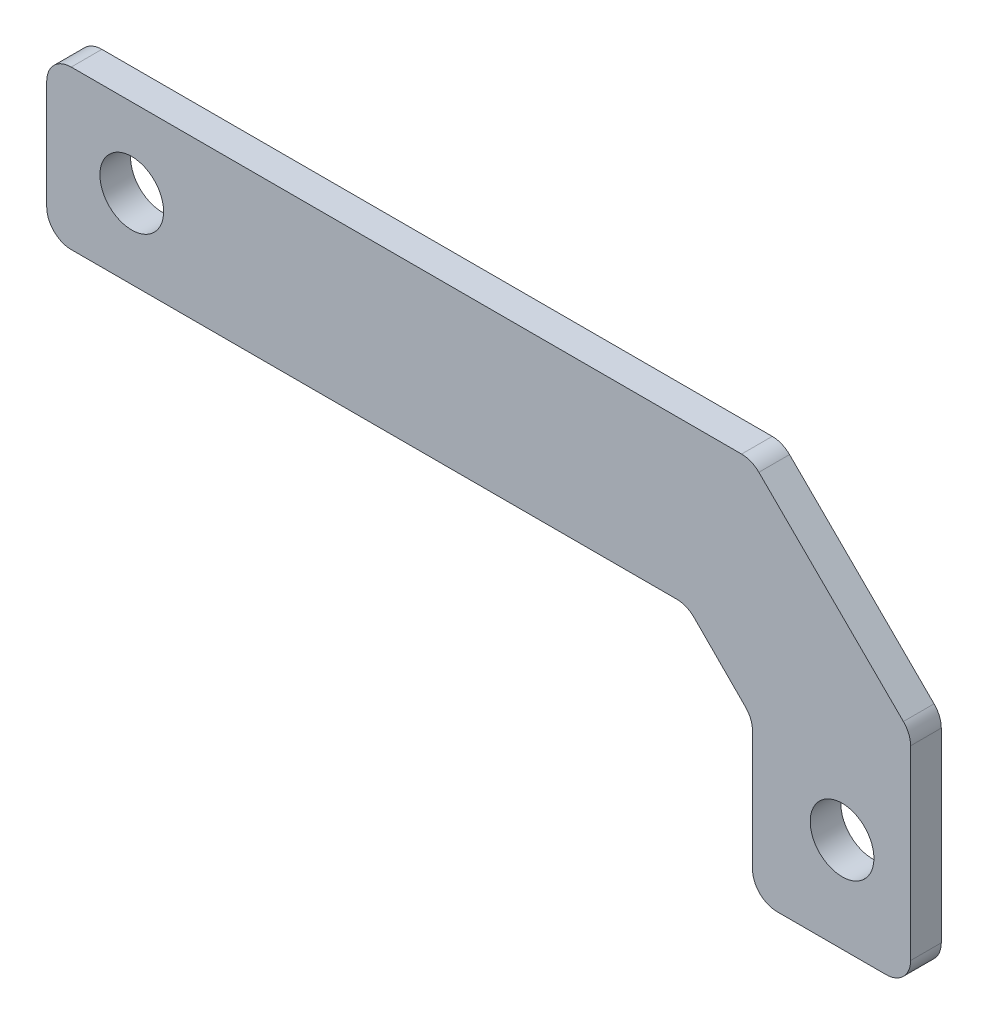
SolidWorks part; units mm, degrees
material "3003-H14"
ref_plane "X-Y Datum" through (0, 0, 0) normal (0, 0, 1) x (1, 0, 0)
ref_plane "X-Z Datum" through (0, 0, 0) normal (0, 1, 0) x (1, 0, 0)
ref_plane "Y-Z Datum" through (0, 0, 0) normal (1, 0, 0) x (0, 0, -1)
sketch "Sketch1" plane through (0, 0, 0) normal (0, 0, 1) x (1, 0, 0)
  line L14 (63.6677, -78.4804) -> (47.2058, -62.1236)
  line L15 (-25.8192, -70.3126) -> (62.0408, -70.3126) construction
  line L20 (40.4961, -78.5016) -> (-25.8192, -78.5016)
  line L22 (47.2058, -62.1236) -> (-25.8192, -62.1236)
  line L23 (-25.8192, -78.5016) -> (-25.8192, -62.1236)
  line L25 (63.6677, -78.4804) -> (63.6677, -101.3404)
  line L26 (63.6677, -101.3404) -> (47.2897, -101.3404)
  line L27 (47.2897, -85.3384) -> (47.2897, -101.3404)
  line L28 (55.4368, -70.302) -> (43.8929, -81.92) construction
  line L29 (40.4961, -78.5016) -> (47.2897, -85.3384)
  circle A0 centre (10, -8.189) radius 4 construction
  point P4 (-17.0119, -70.3126)
  point P9 (94.5499, -37.3736)
  point P10 (56.5659, -91.5356)
  point P25 (43.8929, -81.92)
  point P26 (94.5499, -37.3736)
  dimension "D3" = 8
  dimension "D1" = 16.378
  dimension "D2" = 22.86
  dimension "D4" = 16.378
  dimension "D6" = 16.378
  dimension "D7" = 16.002
  dimension "D8" = 73.025
base flange "Base-Flange1" sketch "Sketch1" thickness 3.175 reverse thickness direction no parameters "D1"=0.7366
hole_wizard "M6 Clearance Hole1" positions "Sketch19" profile "Sketch20" hole size "M6" standard "ANSI Metric" end condition through all
sketch "Sketch19" plane through (0, 0, 0) normal (0, 0, 1) x (1, 0, 0)
  point P3 (56.5659, -91.5356)
  point P9 (-17.0119, -70.3126)
sketch "Sketch20" plane through (56.5659, -91.5356, 0) normal (1, 0, 0) x (0, -1, 0)
  line L0 (0, 0) -> (0, 3.175)
  line L1 (0, 3.175) -> (3.3, 3.175)
  line L2 (3.3, 3.175) -> (3.3, 0)
  line L5 (3.3, 0) -> (0, 0)
  line L11 (0, -6.35) -> (0, 107.95) construction
  dimension "Thru Hole Dia." = 6.6
  dimension "Thru Hole Depth" = 3.175
fillet "Fillet1" radius 2.54 8 edges at (63.6677, -101.3404, -1.5875) (47.2897, -101.3404, -1.5875) (-25.8192, -62.1236, -1.5875) (-25.8192, -78.5016, -1.5875) (47.2058, -62.1236, -1.5875) (63.6677, -78.4804, -1.5875) (47.2897, -85.3384, -1.5875) (40.4961, -78.5016, -1.5875)
sketch "Bend-Lines1" [suppressed] plane through (0, 0, 0) normal (0, 1, 0) x (1, 0, 0)
sketch "Bounding-Box1" [suppressed] plane through (0, 0, 0) normal (0, 1, 0) x (1, 0, 0)
sheet metal parameters "Sheet-Metal3" thickness 3.175 parameters "D1"=0.7366
flat pattern "Flat-Pattern3" [suppressed]
sketch "Bend-Lines2" plane through (0, 0, 0) normal (0, 1, 0) x (1, 0, 0)
sketch3d "Bounding-Box2" [suppressed]
  line L0 (0, -16.378, 0) -> (-76.2, -16.378, 0) construction
  line L1 (0, 0, 0) -> (-76.2, 0, 0) construction
  line L2 (0, -16.378, 0) -> (0, 0, 0) construction
  line L3 (-76.2, -16.378, 0) -> (-76.2, 0, 0) construction
sheet metal parameters "Sheet-Metal8" thickness 3.175 parameters "D1"=0.7366
flat pattern "Flat-Pattern3"
sketch "Bend-Lines2" plane through (0, 0, 0) normal (0, 0, 1) x (1, 0, 0)
sketch3d "Bounding-Box2" [suppressed]
  line L0 (-18.7722, -41.7186, 0) -> (72.6945, -70.2923, 0) construction
  line L1 (-29.6765, -76.6241, 0) -> (61.7902, -105.1978, 0) construction
  line L2 (-18.7722, -41.7186, 0) -> (-29.6765, -76.6241, 0) construction
  line L3 (72.6945, -70.2923, 0) -> (61.7902, -105.1978, 0) construction
